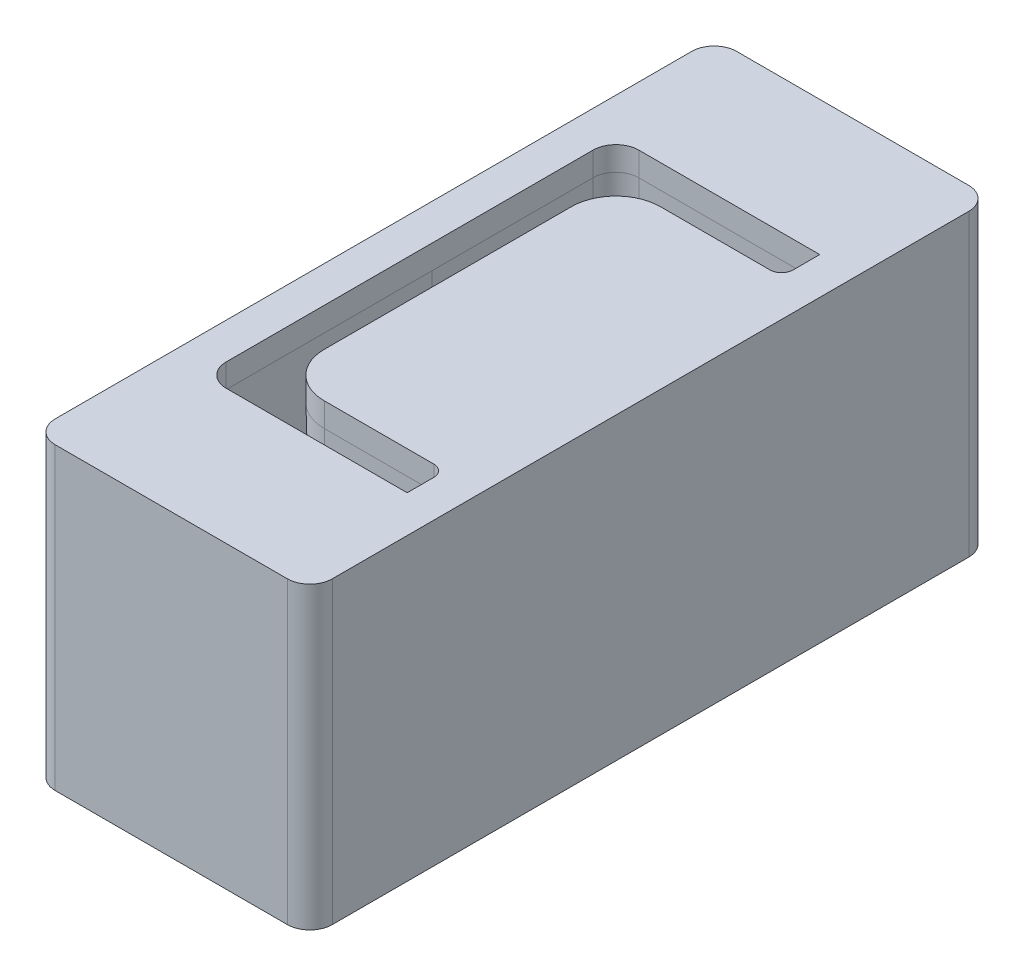
SolidWorks part; units mm, degrees
material "K110"
ref_plane "Front Plane" through (0, 0, 0) normal (0, 0, 1) x (1, 0, 0)
ref_plane "Top Plane" through (0, 0, 0) normal (0, 1, 0) x (1, 0, 0)
ref_plane "Right Plane" through (0, 0, 0) normal (1, 0, 0) x (0, 0, -1)
sketch "Sketch1" plane through (0, 0, 0) normal (0, 1, 0) x (1, 0, 0)
  line L1 (-8, -48.5) -> (29, -48.5)
  line L2 (-8, -48.5) -> (-8, 42.5)
  line L3 (-8, 42.5) -> (29, 42.5)
  line L4 (29, -48.5) -> (29, 42.5)
  line L5 (10.5, 42.5) -> (10.5, -48.5) construction
  line L6 (26, 42.5) -> (-5, 42.5) construction
  line L8 (-5, -48.5) -> (26, -48.5) construction
  line L9 (29, -3) -> (-8, -3) construction
  line L10 (29, -45.5) -> (29, 39.5) construction
  line L11 (-8, 39.5) -> (-8, -45.5) construction
  point P0 (0, 0)
extrude "Boss-Extrude1" add sketch "Sketch1" against normal blind 40
fillet "Fillet1" radius 3 4 edges at (-8, -20, -42.5) (29, -20, -42.5) (29, -20, 48.5) (-8, -20, 48.5)
sketch "Sketch2" plane through (0, 0, 0) normal (0, 1, 0) x (1, 0, 0)
  line L46 (24.05, 24.55) -> (-0.12, 24.55)
  line L47 (24.05, 21) -> (24.05, 24.55)
  line L48 (7.88, 19.45) -> (22.5, 19.45)
  line L49 (1.93, -19.5) -> (1.93, 13.5)
  line L60 (22.5, -25.45) -> (7.88, -25.45)
  line L61 (24.05, -30.55) -> (24.05, -27)
  line L62 (-0.12, -30.55) -> (24.05, -30.55)
  line L63 (-3.17, 21.5) -> (-3.17, -27.5)
  line L64 (24.05, 24.55) -> (-0.12, 24.55)
  line L65 (24.05, 21) -> (24.05, 24.55)
  line L66 (7.88, 19.45) -> (22.5, 19.45)
  line L67 (1.93, -19.5) -> (1.93, 13.5)
  line L68 (22.5, -25.45) -> (7.88, -25.45)
  line L69 (24.05, -30.55) -> (24.05, -27)
  line L70 (-0.12, -30.55) -> (24.05, -30.55)
  line L71 (-3.17, 21.5) -> (-3.17, -27.5)
  arc A36 (-0.12, 24.55) -> (-3.17, 21.5) centre (-0.12, 21.5) ccw
  arc A37 (22.5, 19.45) -> (24.05, 21) centre (22.5, 21) ccw
  arc A38 (7.88, 19.45) -> (1.93, 13.5) centre (7.88, 13.5) ccw
  arc A39 (1.93, -19.5) -> (7.88, -25.45) centre (7.88, -19.5) ccw
  arc A40 (24.05, -27) -> (22.5, -25.45) centre (22.5, -27) ccw
  arc A41 (-3.17, -27.5) -> (-0.12, -30.55) centre (-0.12, -27.5) ccw
  arc A42 (-0.12, 24.55) -> (-3.17, 21.5) centre (-0.12, 21.5) ccw
  arc A43 (22.5, 19.45) -> (24.05, 21) centre (22.5, 21) ccw
  arc A44 (7.88, 19.45) -> (1.93, 13.5) centre (7.88, 13.5) ccw
  arc A45 (1.93, -19.5) -> (7.88, -25.45) centre (7.88, -19.5) ccw
  arc A46 (24.05, -27) -> (22.5, -25.45) centre (22.5, -27) ccw
  arc A47 (-3.17, -27.5) -> (-0.12, -30.55) centre (-0.12, -27.5) ccw
  dimension "D1" = 0.05
extrude "Cut-Extrude1" cut sketch "Sketch2" against normal up to next
sketch "Sketch3" plane through (0, 0, 0) normal (0, 0, 1) x (1, 0, 0)
  line L0 (-3.17, -3.2) -> (-3.8123, -40)
  line L2 (-5, -40) -> (26, -40) construction
  line L3 (-3.8123, -40) -> (-3.17, -40)
  line L4 (-3.17, -40) -> (-3.17, -3.2)
  line L5 (20.35, 0) -> (-20.35, 0) construction
  line L7 (-3.17, -40) -> (-3.17, 0) construction
  dimension "D1" = 1
  dimension "D2" = 3.2
sketch "Sketch4" plane through (0, 0, 0) normal (0, 1, 0) x (1, 0, 0)
  line L16 (24.05, 21) -> (24.05, 24.55) construction
  line L17 (24.05, -30.55) -> (24.05, -27) construction
  line L18 (22.5, -25.45) -> (7.88, -25.45) construction
  line L19 (1.93, -19.5) -> (1.93, 13.5) construction
  line L20 (7.88, 19.45) -> (22.5, 19.45) construction
  line L21 (-0.12, -30.55) -> (24.05, -30.55) construction
  line L22 (-3.17, 21.5) -> (-3.17, -27.5) construction
  line L23 (24.05, 24.55) -> (-0.12, 24.55) construction
  line L24 (24.05, 21) -> (24.05, 24.55)
  line L25 (24.05, -30.55) -> (24.05, -27)
  line L26 (22.5, -25.45) -> (7.88, -25.45)
  line L27 (1.93, -19.5) -> (1.93, 13.5)
  line L28 (7.88, 19.45) -> (22.5, 19.45)
  line L29 (-0.12, -30.55) -> (24.05, -30.55)
  line L30 (-3.17, 21.5) -> (-3.17, -27.5)
  line L31 (24.05, 24.55) -> (-0.12, 24.55)
  arc A12 (22.5, 19.45) -> (24.05, 21) centre (22.5, 21) ccw construction
  arc A13 (24.05, -27) -> (22.5, -25.45) centre (22.5, -27) ccw construction
  arc A14 (1.93, -19.5) -> (7.88, -25.45) centre (7.88, -19.5) ccw construction
  arc A15 (7.88, 19.45) -> (1.93, 13.5) centre (7.88, 13.5) ccw construction
  arc A16 (-3.17, -27.5) -> (-0.12, -30.55) centre (-0.12, -27.5) ccw construction
  arc A17 (-0.12, 24.55) -> (-3.17, 21.5) centre (-0.12, 21.5) ccw construction
  arc A18 (22.5, 19.45) -> (24.05, 21) centre (22.5, 21) ccw
  arc A19 (24.05, -27) -> (22.5, -25.45) centre (22.5, -27) ccw
  arc A20 (1.93, -19.5) -> (7.88, -25.45) centre (7.88, -19.5) ccw
  arc A21 (7.88, 19.45) -> (1.93, 13.5) centre (7.88, 13.5) ccw
  arc A22 (-3.17, -27.5) -> (-0.12, -30.55) centre (-0.12, -27.5) ccw
  arc A23 (-0.12, 24.55) -> (-3.17, 21.5) centre (-0.12, 21.5) ccw
sweep "Cut-Sweep1" cut profiles "Sketch3" path "Sketch4"
hole_wizard "M8 Tapped Hole1" positions "Sketch7" profile "Sketch6" tap size "M8" standard "ISO"
sketch "Sketch7" plane through (0, -40, 0) normal (0, -1, 0) x (-1, 0, 0)
  line L0 (-10.5, 42.5) -> (-10.5, 25.1923) construction
  line L1 (-26, 42.5) -> (5, 42.5) construction
  line L4 (-10.5, -48.5) -> (-10.5, -31.1923) construction
  line L5 (5, -48.5) -> (-26, -48.5) construction
  line L8 (0.12, 25.1923) -> (-24.6923, 25.1923) construction
  line L9 (-24.6923, -31.1923) -> (0.12, -31.1923) construction
  point P0 (-10.5, 33.8462)
  point P2 (-10.5, -39.8462)
sketch "Sketch6" plane through (10.5, -40, -33.8462) normal (1, 0, 0) x (0, 0, -1)
  line L0 (0, 0) -> (0, 24.2929)
  line L1 (0, 24.2929) -> (3.4, 22.25)
  line L2 (3.4, 22.25) -> (3.4, 0)
  line L5 (3.4, 0) -> (0, 0)
  line L10 (0, 24.2929) -> (-3.4, 22.25) construction
  line L11 (0, -6.35) -> (0, 107.95) construction
  dimension "Tap Drill Dia." = 6.8
  dimension "Tap Drill Depth" = 22.25
  dimension "Drill Angle" = 118
cosmetic thread "Hole Thread1"
cosmetic thread "Hole Thread2"
